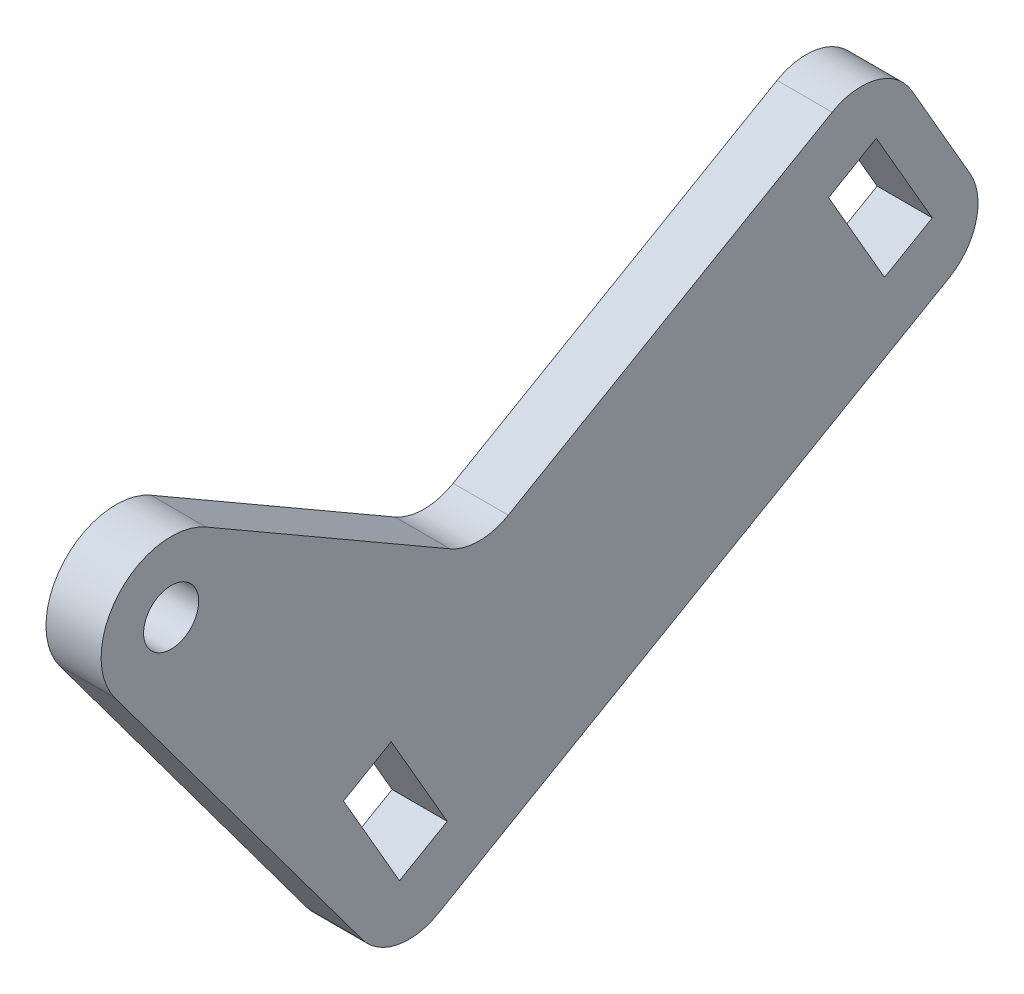
SolidWorks part; units mm, degrees
ref_plane "Front Plane" through (0, 0, 0) normal (0, 0, 1) x (1, 0, 0)
ref_plane "Top Plane" through (0, 0, 0) normal (0, 1, 0) x (1, 0, 0)
ref_plane "Right Plane" through (0, 0, 0) normal (1, 0, 0) x (0, 0, -1)
sketch "Sketch1" plane through (0, 0, 0) normal (1, 0, 0) x (0, 0, -1)
  line L0 (-13.3228, -15.0243) -> (-19.6728, -4.0257)
  line L1 (-13.3228, -15.0243) -> (19.6728, 4.0257)
  line L2 (-19.6728, -4.0257) -> (13.3228, 15.0243)
  line L3 (19.6728, 4.0257) -> (13.3228, 15.0243)
  line L4 (-13.3228, -15.0243) -> (13.3228, 15.0243) construction
  line L5 (-19.6728, -4.0257) -> (19.6728, 4.0257) construction
  line L6 (0, 0) -> (-25.414, 0) construction
  line L7 (-13.1982, -7.62) -> (13.1982, 7.62) construction
  line L9 (48.8706, -8.4463) -> (-17.1206, -46.5463) construction
  line L12 (15.875, -27.4963) -> (0, 0) construction
  line L13 (13.3228, 15.0243) -> (48.8706, -8.4463) construction
  line L14 (-19.6728, -4.0257) -> (-17.1206, -46.5463) construction
  line L15 (46.1209, -10.0338) -> (42.9459, -4.5345) construction
  line L16 (-41.8965, 50.8) -> (41.8965, 50.8) construction
  line L17 (0, 50.8) -> (0, 0) construction
  line L18 (13.3228, 15.0243) -> (-21.356, 15.0243) construction
  point P1 (0, 0)
  line B0 (-12.9098, -11.1196) -> (-10.3117, -9.6196)
  line B1 (-12.9098, -11.1196) -> (-16.0848, -5.6204)
  line B2 (-16.0848, -5.6204) -> (-13.4867, -4.1204)
  line B3 (-10.3117, -9.6196) -> (-13.4867, -4.1204)
  line B4 (-12.9098, -11.1196) -> (-13.4867, -4.1204) construction
  line B5 (-16.0848, -5.6204) -> (-10.3117, -9.6196) construction
  line B6 (13.4867, 4.1204) -> (16.0848, 5.6204)
  line B7 (13.4867, 4.1204) -> (10.3117, 9.6196)
  line B8 (10.3117, 9.6196) -> (12.9098, 11.1196)
  line B9 (16.0848, 5.6204) -> (12.9098, 11.1196)
  line B10 (13.4867, 4.1204) -> (12.9098, 11.1196) construction
  line B11 (10.3117, 9.6196) -> (16.0848, 5.6204) construction
  dimension "D1" = 12.7
  dimension "D2" = 38.1
  dimension "D3" = 30
  dimension "D4" = 3.81
  dimension "D5" = 76.2
  dimension "D6" = 6.35
  dimension "D7" = 3.175
  dimension "D8" = 50.8
sketch_block_instance "Block1-1"
sketch_block "Block1" parameters "D1"=3, "D2"=6.35
sketch_block_instance "Block1-2"
sketch "Sketch2" plane through (0, 0, 0) normal (1, 0, 0) x (0, 0, -1)
  line L6 (-16.0213, -5.7304) -> (-12.9733, -11.0096)
  line L7 (-16.0213, -5.7304) -> (-13.4232, -4.2304)
  line L8 (-12.9733, -11.0096) -> (-10.3752, -9.5096)
  line L9 (-13.4232, -4.2304) -> (-10.3752, -9.5096)
  line L10 (-16.0213, -5.7304) -> (-10.3752, -9.5096) construction
  line L11 (-12.9733, -11.0096) -> (-13.4232, -4.2304) construction
  line L12 (10.3752, 9.5096) -> (13.4232, 4.2304)
  line L13 (10.3752, 9.5096) -> (12.9733, 11.0096)
  line L14 (13.4232, 4.2304) -> (16.0213, 5.7304)
  line L15 (12.9733, 11.0096) -> (16.0213, 5.7304)
  line L16 (10.3752, 9.5096) -> (16.0213, 5.7304) construction
  line L17 (13.4232, 4.2304) -> (12.9733, 11.0096) construction
  line L19 (-19.6728, -4.0257) -> (13.3228, 15.0243)
  line L20 (13.3228, 15.0243) -> (19.6728, 4.0257)
  line L21 (-3.175, 5.4993) -> (0, 0) construction
  line L22 (-13.1982, -7.62) -> (13.1982, 7.62) construction
  line L24 (19.6728, 4.0257) -> (-13.3228, -15.0243)
  line L27 (-10.3117, -9.6196) -> (-13.4867, -4.1204) construction
  line L28 (-13.3228, -15.0243) -> (-19.6728, -4.0257)
  line L29 (15.875, -27.4963) -> (0, 0) construction
  line L30 (-13.1982, -7.62) -> (-16.4978, -9.525) construction
  point P11 (-13.1982, -7.62)
  point P12 (13.1982, 7.62)
  dimension "D1" = 3
  dimension "D2" = 6.096
  dimension "D3" = 12.7
  dimension "D4" = 38.1
extrude "Boss-Extrude1" add sketch "Sketch2" along normal mid plane 3
sketch "Sketch3" plane through (0, 0, 0) normal (1, 0, 0) x (0, 0, -1)
  line L0 (-25.4, 7.62) -> (71.9673, -21.4001) construction
  line L1 (-25.4, 7.62) -> (75.1092, 22.468) construction
  circle A0 centre (-25.4, 7.62) radius 1.5
  arc A1 (71.9673, -21.4001) -> (75.1092, 22.468) centre (-25.4, 7.62) ccw construction
  arc A2 (73.4048, -21.8286) -> (76.5931, 22.6873) centre (-25.4, 7.62) ccw
  arc A3 (70.5298, -20.9717) -> (73.6253, 22.2488) centre (-25.4, 7.62) ccw
  arc A4 (70.5298, -20.9717) -> (73.4048, -21.8286) centre (71.9673, -21.4001) ccw
  arc A5 (76.5931, 22.6873) -> (73.6253, 22.2488) centre (75.1092, 22.468) ccw
  circle A6 centre (-25.4, 7.62) radius 3.81
  arc A7 (71.9673, -21.4001) -> (75.1092, 22.468) centre (-25.4, 7.62) ccw construction
  arc A8 (75.6186, -22.4884) -> (78.8783, 23.0248) centre (-25.4, 7.62) ccw
  arc A9 (68.316, -20.3119) -> (71.3401, 21.9112) centre (-25.4, 7.62) ccw
  arc A10 (68.316, -20.3119) -> (75.6186, -22.4884) centre (71.9673, -21.4001) ccw
  arc A11 (78.8783, 23.0248) -> (71.3401, 21.9112) centre (75.1092, 22.468) ccw
  point P4 (75.9404, 0.3619)
  point P14 (75.9404, 0.3619)
  dimension "D1" = 3
  dimension "D2" = 3
  dimension "D3" = 7.62
  dimension "D4" = 7.62
  dimension "D5" = 25
  dimension "D6" = 101.6
  dimension "D7" = 25.4
  dimension "D8" = 7.62
extrude "Boss-Extrude2" add sketch "Sketch3" along normal mid plane 3 separate body contours A6 A0 region at (0, 7.62, 29.1022)
sketch "Sketch4" plane through (1.5, 0, 0) normal (1, 0, 0) x (0, 0, -1)
  line L0 (-13.3228, -15.0243) -> (-28.4583, 5.3478)
  line L1 (-23.495, 10.9196) -> (-8.6409, 2.3435)
  line L3 (-13.3228, -15.0243) -> (-19.6728, -4.0257)
  line L4 (-19.6728, -4.0257) -> (13.3228, 15.0243)
  line L5 (13.3228, 15.0243) -> (19.6728, 4.0257)
  circle A4 centre (-25.4, 7.62) radius 3.81 construction
  circle A5 centre (-25.4, 7.62) radius 3.81
  line M13 (-19.6728, -4.0257) -> (-13.3228, -15.0243)
  line M16 (13.3228, 15.0243) -> (-19.6728, -4.0257)
  dimension "D1" = 60
extrude "Boss-Extrude3" add sketch "Sketch4" against normal up to surface (3 mm away) contours L0 M13 M16 region at (1.5, 1.5585, 18.5394) up to face at (-1.5, 0, 0)
fillet "Fillet1" radius 3.175 4 edges at (0, 4.0257, -19.6728) (0, -15.0243, 13.3228) (0, 2.3435, 8.6409) (0, 15.0243, -13.3228)
equation "\"PlateThickness\"=0.11811"
equation "\"D1@Boss-Extrude2\"=\"PlateThickness\""
equation "\"D1@Boss-Extrude1\"=\"PlateThickness\""
